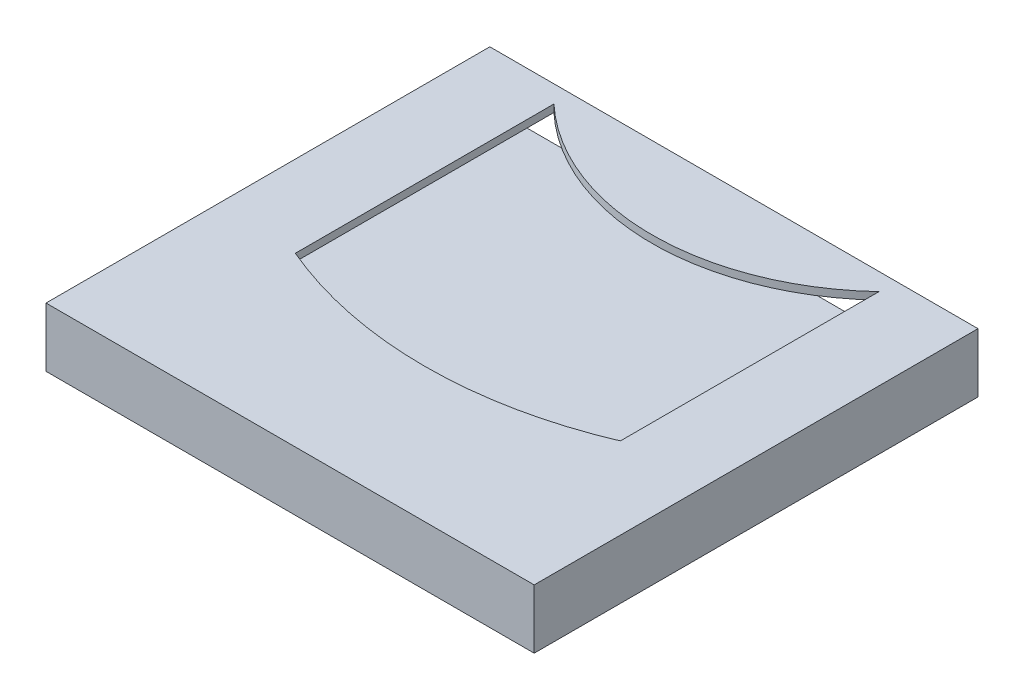
SolidWorks part; units mm, degrees
ref_plane "前视基准面" through (0, 0, 0) normal (0, 0, 1) x (1, 0, 0)
ref_plane "上视基准面" through (0, 0, 0) normal (0, 1, 0) x (1, 0, 0)
ref_plane "右视基准面" through (0, 0, 0) normal (1, 0, 0) x (0, 0, -1)
sketch "草图1" plane through (0, 0, 0) normal (0, 1, 0) x (1, 0, 0)
  line L0 (-59.7364, 0) -> (54.8847, 0) construction
  line L1 (0, 49.4265) -> (0, -41.8458) construction
  line L3 (-16.5, 15) -> (16.5, 15)
  line L4 (-16.5, 15) -> (-16.5, -15)
  line L5 (-16.5, -15) -> (16.5, -15)
  line L6 (16.5, 15) -> (16.5, -15)
  dimension "D1" = 33
  dimension "D2" = 30
extrude "拉伸1" add sketch "草图1" along normal blind 4
shell "抽壳1" thickness 0.5 removed face at (0, 2, -15)
sketch "草图2" plane through (0, 4, 0) normal (0, 1, 0) x (-1, 0, 0)
  line L0 (0, -18.1348) -> (0, 20.3596) construction
  line L1 (21.045, 3.6581) -> (-22.4579, 3.6581) construction
  line L2 (10.9856, -13.8199) -> (10.9856, 3.6581)
  line L3 (-10.9856, -13.8199) -> (-10.9856, 3.6581)
  line L4 (13.9317, -13.8199) -> (-11.9423, -13.8199) construction
  arc A0 (10.9856, -13.8199) -> (-10.9856, -13.8199) centre (0, -25.5256) ccw
  arc A1 (10.9856, 3.6581) -> (-10.9856, 3.6581) centre (0, -22.0857) ccw
extrude "切除-拉伸2" cut sketch "草图2" against normal blind 1
